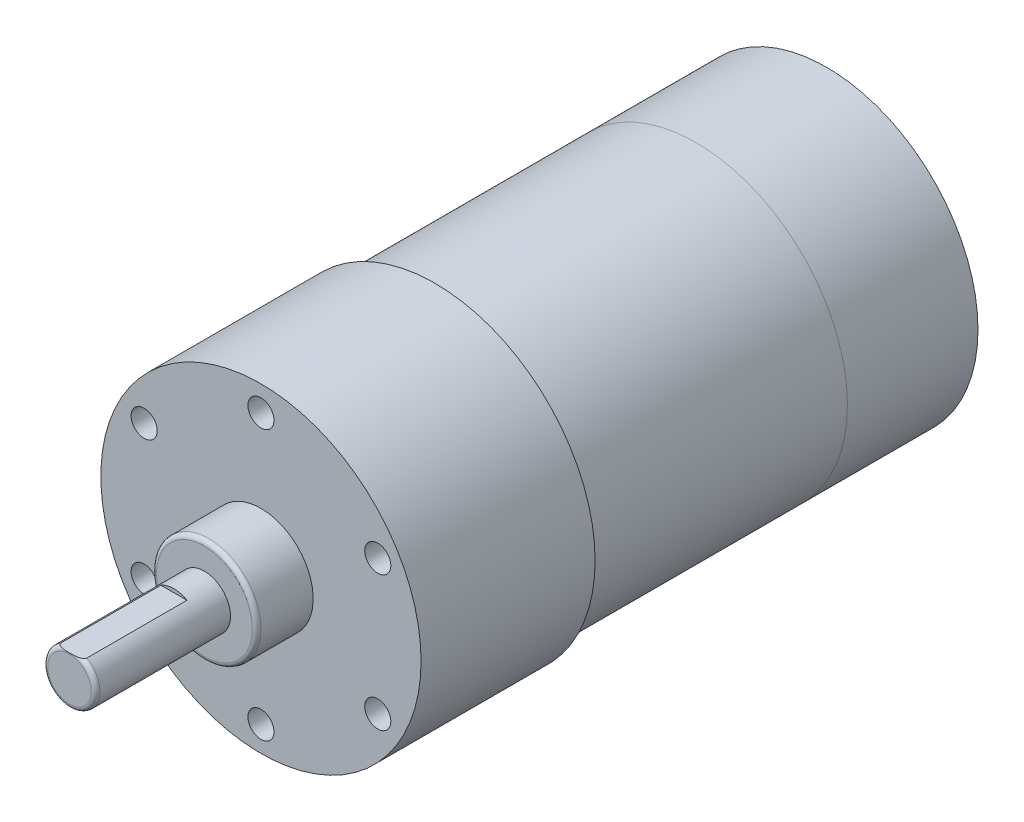
SolidWorks part; units mm, degrees
ref_plane "Front Plane" through (0, 0, 0) normal (0, 0, 1) x (1, 0, 0)
ref_plane "Top Plane" through (0, 0, 0) normal (0, 1, 0) x (1, 0, 0)
ref_plane "Right Plane" through (0, 0, 0) normal (1, 0, 0) x (0, 0, -1)
sketch "Sketch1" plane through (0, 0, 0) normal (0, 0, 1) x (1, 0, 0)
  circle A0 centre (0, 0) radius 18.4
  dimension "D1" = 36.8
extrude "Boss-Extrude1" add sketch "Sketch1" along normal blind 20
sketch "Sketch2" plane through (0, 0, 0) normal (0, 0, -1) x (-1, 0, 0)
  circle A0 centre (0, 0) radius 17.4
  dimension "D1" = 34.8
extrude "Boss-Extrude2" add sketch "Sketch2" along normal blind 30
sketch "Sketch3" plane through (0, 0, 20) normal (0, 0, 1) x (1, 0, 0)
  circle A0 centre (0, 0) radius 6
  point P2 (0, 0)
  dimension "D1" = 12
extrude "Boss-Extrude3" add sketch "Sketch3" along normal blind 6.5
fillet "Fillet1" radius 0.5 1 edges at (6, 0, 26.5)
sketch "Sketch4" plane through (0, 0, 26.5) normal (0, 0, 1) x (1, 0, 0)
  line L0 (0, -6.8172) -> (0, 7.1125) construction
  circle A0 centre (0, 0) radius 3
  dimension "D1" = 6
extrude "Boss-Extrude4" add sketch "Sketch4" along normal blind 15.5
sketch "Sketch5" plane through (0, 0, 42) normal (0, 0, 1) x (1, 0, 0)
  line L0 (-1.4967, 2.6) -> (1.4967, 2.6)
  line L1 (0, -3) -> (9.3109, -3) construction
  circle A0 centre (0, 0) radius 3 construction
  circle A1 centre (0, 0) radius 3 construction
  arc A2 (1.4967, 2.6) -> (-1.4967, 2.6) centre (0, 0) ccw
  dimension "D1" = 5.6
extrude "Cut-Extrude1" cut sketch "Sketch5" against normal blind 12
hole_wizard "Ø3.0 (3) Diameter Hole1" positions "Sketch7" profile "Sketch6" hole size "Ø3.0" standard "Ansi Metric"
sketch "Sketch7" plane through (0, 0, 20) normal (0, 0, 1) x (1, 0, 0)
  point P0 (-13.4234, 7.75)
  point P1 (-13.4234, -7.75)
  point P3 (0, -15.5)
  point P5 (13.4234, 7.75)
  point P7 (0, 15.5)
  point P22 (13.4234, -7.75)
  dimension "D1" = 15.5
  dimension "D2" = 15.5
  dimension "D3" = 15.5
  dimension "D4" = 15.5
  dimension "D5" = 15.5
  dimension "D6" = 15.5
  dimension "D7" = 15.5
  dimension "D8" = 15.5
  dimension "D9" = 15.5
  dimension "D10" = 15.5
sketch "Sketch6" plane through (-13.4234, 7.75, 20) normal (1, 0, 0) x (0, -1, 0)
  line L0 (0, 0) -> (0, 3.9013)
  line L1 (0, 3.9013) -> (1.5, 3)
  line L2 (1.5, 3) -> (1.5, 0)
  line L5 (1.5, 0) -> (0, 0)
  line L10 (0, 3.9013) -> (-1.5, 3) construction
  line L11 (0, -6.35) -> (0, 107.95) construction
  dimension "Hole Dia." = 3
  dimension "Hole Depth" = 3
  dimension "Drill Angle" = 118
ref_plane "Plane1" through (0, 0, -33) normal (0, 0, -1) x (-1, 0, 0)
fillet "Fillet4" radius 0.5 1 edges at (0, -3, 42)
sketch "Croquis1" plane through (0, 0, -30) normal (0, 0, -1) x (-1, 0, 0)
  circle A1 centre (0, 0) radius 17.4
extrude "Saliente-Extruir3" add sketch "Croquis1" along normal blind 15 separate body
